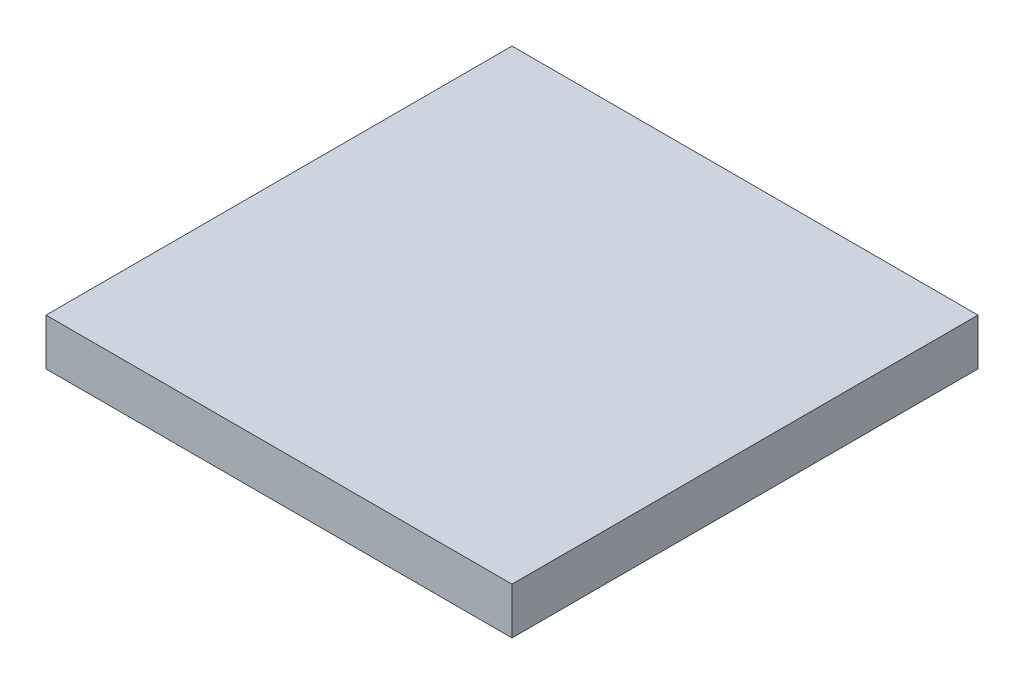
SolidWorks part; units mm, degrees
material "Cast Stainless Steel"
ref_plane "Front Plane" through (0, 0, 0) normal (0, 0, 1) x (1, 0, 0)
ref_plane "Top Plane" through (0, 0, 0) normal (0, 1, 0) x (1, 0, 0)
ref_plane "Right Plane" through (0, 0, 0) normal (1, 0, 0) x (0, 0, -1)
other "Configuration Table"
sketch "Sketch1" plane through (0, 0, 0) normal (0, 1, 0) x (1, 0, 0)
  line L0 (-25, -25) -> (25, 25) construction
  line L1 (-25, -25) -> (25, -25)
  line L2 (-25, -25) -> (-25, 25)
  line L3 (-25, 25) -> (25, 25)
  line L4 (25, -25) -> (25, 25)
  dimension "D1" = 50
  dimension "D2" = 50
sheet metal parameters "Sheet-Metal1" thickness 5 parameters "D1"=0.7366
base flange "Base-Flange1" sketch "Sketch1" thickness 5 reverse thickness direction yes parameters "D1"=0.7366
flat pattern "Flat-Pattern1" [suppressed]
sketch "Bend-Lines1" plane through (0, 0, 0) normal (0, 1, 0) x (-1, 0, 0)
